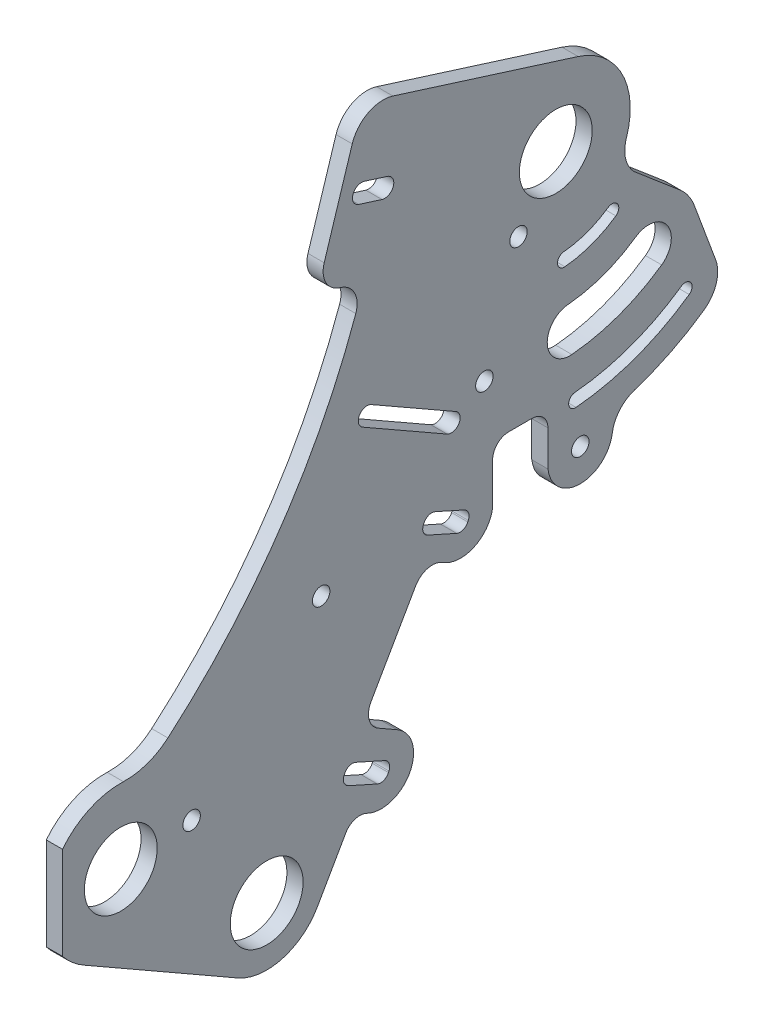
SolidWorks part; units mm, degrees
ref_plane "Front Plane" through (0, 0, 0) normal (0, 0, 1) x (1, 0, 0)
ref_plane "Top Plane" through (0, 0, 0) normal (0, 1, 0) x (1, 0, 0)
ref_plane "Right Plane" through (0, 0, 0) normal (1, 0, 0) x (0, 0, -1)
sketch "Sketch1" plane through (0, 0, 0) normal (1, 0, 0) x (0, 0, -1)
  line L0 (0, 0) -> (-57.2178, 40.0643) construction
  line L1 (55, 0) -> (-55, 0) construction
  line L2 (0, 0) -> (113.3671, 198.5091) construction
  line L3 (113.3671, 198.5091) -> (49.679, 218.5899) construction
  line L4 (99.338, 182.3162) -> (24.13, 14.224) construction
  line L5 (30.5555, 28.5852) -> (30.3602, 28.1486)
  line L6 (36.1341, 219.132) -> (45.2183, 216.2678)
  line L7 (38.2727, 225.9148) -> (47.3569, 223.0506)
  line L8 (34.9378, 30.2582) -> (46.2714, 25.1873)
  line L9 (47.9444, 20.8051) -> (47.749, 20.3685)
  line L10 (43.3668, 18.6955) -> (32.0332, 23.7664)
  line L11 (113.3671, 198.5091) -> (121.0867, 110.2733) construction
  line L12 (113.3671, 198.5091) -> (164.1704, 125.9544) construction
  line L13 (0, 55) -> (0, -55) construction
  line L14 (61.6761, 98.1406) -> (61.4807, 97.704)
  line L15 (66.0583, 99.8136) -> (77.3919, 94.7427)
  line L16 (79.0649, 90.3605) -> (78.8696, 89.9239)
  line L17 (74.4873, 88.2509) -> (63.1537, 93.3218)
  line L18 (72.429, 126.8253) -> (39.3441, 145.7198) construction
  line L19 (98.7442, 176.9048) -> (85.3778, 134.5121) construction
  line L20 (70.7285, 123.8476) -> (37.6436, 142.7421)
  line L21 (74.1295, 129.8029) -> (41.0446, 148.6974)
  line L22 (85.3778, 134.5121) -> (54.8261, 37.6144) construction
  circle A0 centre (0, 0) radius 14.2875
  circle A1 centre (-57.2178, 40.0643) radius 14.2875
  circle A2 centre (113.3671, 198.5091) radius 14.2875
  arc A3 (45.2183, 216.2678) -> (47.3569, 223.0506) centre (46.2876, 219.6592) ccw
  arc A4 (38.2727, 225.9148) -> (36.1341, 219.132) centre (37.2034, 222.5234) ccw
  arc A5 (118.1267, 144.1069) -> (119.6763, 126.3946) centre (118.9015, 135.2507) ccw
  arc A6 (116.4838, 162.8851) -> (116.9487, 157.5713) centre (116.7162, 160.2282) ccw
  arc A7 (120.8543, 112.9301) -> (121.3192, 107.6164) centre (121.0867, 110.2733) ccw
  arc A8 (154.8883, 139.2107) -> (144.6901, 153.7752) centre (149.7892, 146.4929) ccw
  arc A9 (136.9377, 164.8468) -> (133.8783, 169.2161) centre (135.408, 167.0314) ccw
  arc A10 (165.7001, 123.7698) -> (162.6407, 128.1391) centre (164.1704, 125.9544) ccw
  arc A11 (144.6901, 153.7752) -> (118.1267, 144.1069) centre (113.3671, 198.5091) cw
  arc A12 (154.8883, 139.2107) -> (119.6763, 126.3946) centre (113.3671, 198.5091) cw
  arc A13 (133.8783, 169.2161) -> (116.4838, 162.8851) centre (113.3671, 198.5091) cw
  arc A14 (136.9377, 164.8468) -> (116.9487, 157.5713) centre (113.3671, 198.5091) cw
  arc A15 (162.6407, 128.1391) -> (120.8543, 112.9301) centre (113.3671, 198.5091) cw
  arc A16 (165.7001, 123.7698) -> (121.3192, 107.6164) centre (113.3671, 198.5091) cw
  arc A17 (46.2714, 25.1873) -> (47.9444, 20.8051) centre (44.9167, 22.1597) cw
  arc A18 (47.749, 20.3685) -> (43.3668, 18.6955) centre (44.7214, 21.7231) cw
  arc A19 (32.0332, 23.7664) -> (30.3602, 28.1486) centre (33.3878, 26.794) cw
  arc A20 (30.5555, 28.5852) -> (34.9378, 30.2582) centre (33.5831, 27.2306) cw
  arc A21 (74.4873, 88.2509) -> (78.8696, 89.9239) centre (75.842, 91.2785) ccw
  arc A22 (79.0649, 90.3605) -> (77.3919, 94.7427) centre (76.0373, 91.7151) ccw
  arc A23 (63.1537, 93.3218) -> (61.4807, 97.704) centre (64.5084, 96.3494) cw
  arc A24 (61.6761, 98.1406) -> (66.0583, 99.8136) centre (64.7037, 96.786) cw
  circle A25 centre (-29.4365, 42.7262) radius 3.429
  circle A26 centre (21.3635, 93.5262) radius 3.429
  circle A27 centre (122.9635, 93.5262) radius 3.429
  arc A28 (70.7285, 123.8476) -> (74.1295, 129.8029) centre (72.429, 126.8253) ccw
  arc A29 (41.0446, 148.6974) -> (37.6436, 142.7421) centre (39.3441, 145.7198) ccw
  circle A30 centre (98.7442, 176.9048) radius 3.429
  circle A31 centre (85.3778, 134.5121) radius 3.429
  point P47 (49.299, 23.8327)
  point P54 (29.0056, 25.121)
  point P57 (31.9101, 31.6128)
  point P62 (80.4195, 93.3881)
  point P65 (60.1261, 94.6764)
  point P68 (63.0307, 101.1682)
  point P78 (55.8866, 136.2725)
  dimension "D2" = 28.575
  dimension "D4" = 228.6
  dimension "D10" = 13.081
  dimension "D7" = 3.556
  dimension "D8" = 9.525
  dimension "D11" = 65.895
  dimension "D18" = 91.2399
  dimension "D20" = 5.334
  dimension "D21" = 25.0729
  dimension "D27" = 7.112
  dimension "D22" = 8.89
  dimension "D29" = 3.3168
  dimension "D30" = 6.858
  dimension "D33" = 6.858
  dimension "D36" = 6.858
  dimension "D40" = 3.429
  dimension "D43" = 6.858
  dimension "D44" = 6.858
  dimension "D46" = 31.75
  dimension "D1" = 35
  dimension "D3" = 69.85
  dimension "D5" = 60.27
  dimension "D6" = 17.5
  dimension "D9" = 66.7788
  dimension "D12" = 14.224
  dimension "D13" = 184.15
  dimension "D14" = 24.13
  dimension "D15" = 7.112
  dimension "D16" = 165.1
  dimension "D17" = 19.05
  dimension "D19" = 63.5
  dimension "D23" = 19.05
  dimension "D24" = 25.0729
  dimension "D25" = 5
  dimension "D26" = 35
  dimension "D28" = 88.9
  dimension "D31" = 27.7812
  dimension "D32" = 2.6619
  dimension "D34" = 78.5812
  dimension "D35" = 53.4619
  dimension "D37" = 180.1812
  dimension "D38" = 53.4619
  dimension "D39" = 82.55
  dimension "D41" = 38.1
  dimension "D42" = 69.85
  dimension "D45" = 44.45
  dimension "D47" = 101.6
sketch "Sketch2" plane through (0, 0, 0) normal (1, 0, 0) x (0, 0, -1)
  line L0 (-71.7273, 14.7129) -> (-11.3553, -19.8403)
  line L1 (-80.0778, 21.8807) -> (-80.0778, 58.2479)
  line L2 (19.8509, -11.3367) -> (31.0118, 8.2063)
  line L3 (0, 0) -> (113.3671, 198.5091) construction
  line L7 (167.6526, 153.1112) -> (176.0793, 130.3666)
  line L8 (144.0118, 176.3866) -> (162.118, 161.0155)
  line L9 (113.3671, 198.5091) -> (49.679, 218.5899) construction
  line L11 (49.4775, 249.281) -> (122.1507, 226.3672)
  line L12 (33.5463, 240.9877) -> (22.5477, 206.1046)
  line L13 (28.5188, 194.6341) -> (29.0827, 194.4563)
  line L14 (110.3329, 92.1997) -> (110.288, 92.1997)
  line L15 (88.5941, 92.1997) -> (88.5941, 106.1697)
  line L16 (110.288, 92.1997) -> (110.288, 106.1697)
  line L17 (103.938, 112.5197) -> (94.9441, 112.5197)
  line L18 (88.5941, 92.1997) -> (88.5941, 89.8131)
  line L19 (58.4048, 78.4274) -> (40.9124, 47.8643)
  line L20 (43.7407, 37.4658) -> (51.2253, 33.1821)
  arc A0 (-80.0778, 21.8807) -> (-71.7273, 14.7129) centre (-57.2178, 40.0643) ccw
  arc A1 (-11.3553, -19.8403) -> (19.8509, -11.3367) centre (0, 0) ccw
  arc A2 (39.3228, 10.758) -> (51.2253, 33.1821) centre (44.9167, 22.1597) ccw
  arc A3 (69.1503, 81.0446) -> (88.5941, 89.8131) centre (76.0373, 91.7151) ccw
  arc A7 (31.0118, 8.2063) -> (39.3228, 10.758) centre (36.5259, 5.0572) cw
  arc A9 (171.4548, 115.5512) -> (176.0793, 130.3666) centre (164.1704, 125.9544) ccw
  arc A10 (171.4548, 115.5512) -> (144.2404, 102.0569) centre (113.3671, 198.5091) cw
  arc A11 (167.6526, 153.1112) -> (162.118, 161.0155) centre (149.7892, 146.4929) ccw
  arc A13 (141.0737, 189.2588) -> (122.1507, 226.3672) centre (113.3671, 198.5091) ccw
  arc A14 (144.0118, 176.3866) -> (141.0737, 189.2588) centre (153.1201, 185.237) cw
  arc A15 (33.5463, 240.9877) -> (49.4775, 249.281) centre (45.6585, 237.1687) cw
  arc A16 (34.9451, 182.6622) -> (-38.7381, 75.3772) centre (-204.3307, 268.0513) cw
  arc A17 (-56.1886, 69.2562) -> (-80.0778, 58.2479) centre (-57.2178, 40.0643) ccw
  arc A18 (29.0827, 194.4563) -> (34.9451, 182.6622) centre (26.3331, 185.7355) cw
  arc A19 (22.5477, 206.1046) -> (28.5188, 194.6341) centre (31.2685, 203.3549) ccw
  arc A21 (-38.7381, 75.3772) -> (-56.1886, 69.2562) centre (-55.2938, 94.6404) cw
  arc A22 (110.3329, 92.1997) -> (135.5378, 91.7438) centre (122.9635, 93.5262) ccw
  arc A24 (135.5378, 91.7438) -> (144.2404, 102.0569) centre (148.1121, 89.9614) cw
  arc A25 (110.288, 106.1697) -> (103.938, 112.5197) centre (103.938, 106.1697) ccw
  arc A26 (88.5941, 106.1697) -> (94.9441, 112.5197) centre (94.9441, 106.1697) cw
  arc A27 (58.4048, 78.4274) -> (69.1503, 81.0446) centre (65.0182, 74.6423) cw
  arc A28 (43.7407, 37.4658) -> (40.9124, 47.8643) centre (47.5258, 44.0792) cw
  point P24 (84.2401, 101.4107)
  point P27 (71.8548, 79.7236)
  point P30 (46.1964, 34.7951)
  point P41 (110.288, 112.5197)
  point P62 (37.3653, 253.0999)
  point P66 (37.9664, 191.6553)
  point P69 (19.798, 197.3838)
  point P71 (88.5941, 112.5197)
  point P74 (-48.0067, 67.784)
  point P92 (37.1273, 41.2509)
  dimension "D1" = 58.42
  dimension "D2" = 45.72
  dimension "D4" = 25.4
  dimension "D5" = 21.6939
  dimension "D6" = 90
  dimension "D7" = 25.4
  dimension "D8" = 101.2729
  dimension "D9" = 38.1
  dimension "D10" = 6.35
  dimension "D11" = 58.42
  dimension "D13" = 12.7
  dimension "D15" = 12.7
  dimension "D17" = 9.144
  dimension "D18" = 254.0555
  dimension "D19" = 2.3866
  dimension "D20" = 25.4
  dimension "D21" = 25.4
  dimension "D24" = 12.7
  dimension "D28" = 6.35
  dimension "D30" = 7.62
  dimension "D31" = 7.62
  dimension "D3" = 22.86
  dimension "D12" = 88.9
  dimension "D14" = 58.42
  dimension "D16" = 19.05
  dimension "D22" = 180.1812
  dimension "D23" = 53.4619
  dimension "D25" = 20.32
  dimension "D26" = 20.32
  dimension "D27" = 12.6305
  dimension "D29" = 16.2437
extrude "Boss-Extrude1" add sketch "Sketch2" along normal blind 3.175 and the other way blind 3.175
extrude "Cut-Extrude1" cut sketch "Sketch1" against normal through all and the other way through all
